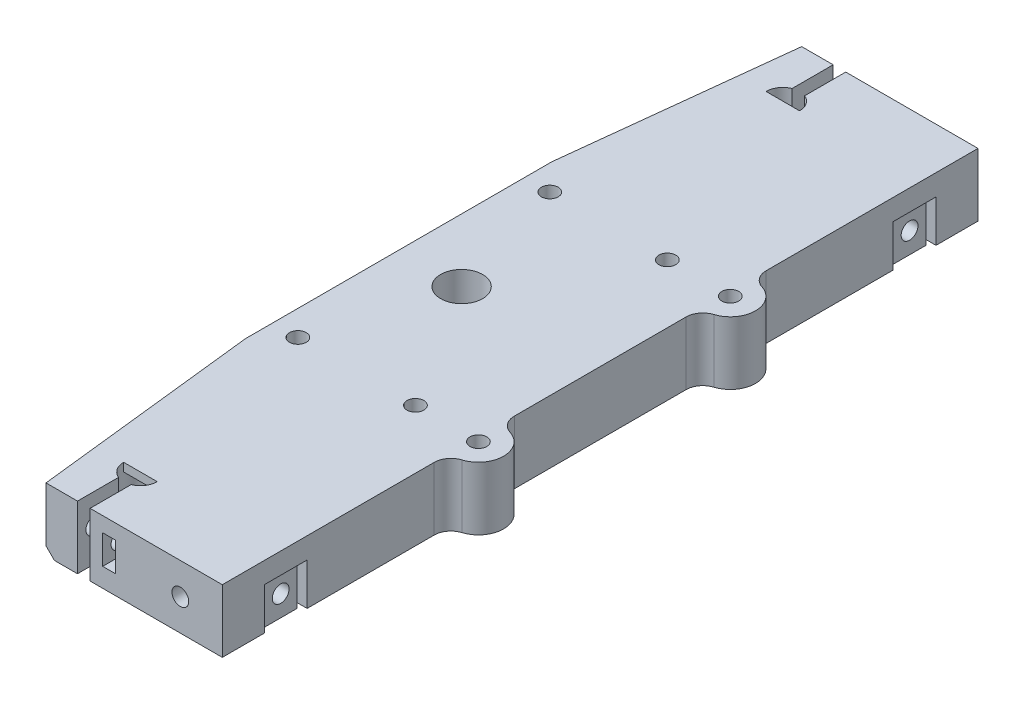
SolidWorks part; units mm, degrees
ref_plane "Płaszczyzna przednia" through (0, 0, 0) normal (0, 0, 1) x (1, 0, 0)
ref_plane "Płaszczyzna górna" through (0, 0, 0) normal (0, 1, 0) x (1, 0, 0)
ref_plane "Płaszczyzna prawa" through (0, 0, 0) normal (1, 0, 0) x (0, 0, -1)
sketch "Szkic1" plane through (0, 0, 0) normal (0, 1, 0) x (1, 0, 0)
  line L0 (-20.5, 36.5) -> (-14.5, 90)
  line L1 (27.5, -90) -> (-14.5, -90)
  line L2 (27.5, -90) -> (27.5, 90)
  line L3 (27.5, 90) -> (-14.5, 90)
  line L4 (-20.5, -36.5) -> (-20.5, 36.5)
  line L5 (27.5, 0) -> (-46.9742, 0) construction
  line L6 (-7, -80.2081) -> (-7, -90)
  line L7 (-20.5, -36.5) -> (-14.5, -90)
  line L8 (-4, -80.2081) -> (-4, -90)
  line L9 (-7, 80.2081) -> (-7, 90)
  line L10 (-4, 80.2081) -> (-4, 90)
  circle A0 centre (-14.5, 30) radius 2
  circle A1 centre (13.5, 30) radius 2
  circle A4 centre (13.5, -30) radius 2
  circle A5 centre (-14.5, -30) radius 2
  circle A6 centre (-5.5, -76.5) radius 4
  circle A7 centre (-5.5, 0) radius 5
  circle A8 centre (-5.5, 76.5) radius 4
  point P0 (0, 0)
  dimension "D7" = 6
  dimension "D10" = 4
  dimension "D11" = 30
  dimension "D12" = 15
  dimension "D13" = 10
  dimension "D16" = 8
  dimension "D1" = 48
  dimension "D2" = 180
  dimension "D3" = 27.5
  dimension "D4" = 90
  dimension "D5" = 42
  dimension "D6" = 73
  dimension "D8" = 28
  dimension "D14" = 13.5
  dimension "D15" = 15
  dimension "D17" = 3
  dimension "D19" = 13.5
  dimension "D20" = 3
extrude "Dodanie-wyciągnięcie1" add sketch "Szkic1" along normal blind 15 contours L2 L5 A7 L4 L7 L1 L6 A6 L8 A5 A4 | L5 L2 L3 L10 A8 L9 L0 L4 A7 A0 A1 region at (4.6694, 0, -43.745) region at (4.6694, 0, 43.745)
sketch "Szkic3" plane through (0, 15, 0) normal (0, 1, 0) x (1, 0, 0)
  line L0 (-9.5, 76.5) -> (-1.5, 76.5)
  line L1 (-9.5, -76.5) -> (-1.5, -76.5)
  arc A0 (-7, 80.2081) -> (-4, 80.2081) centre (-5.5, 76.5) ccw construction
  arc A1 (-4, -80.2081) -> (-7, -80.2081) centre (-5.5, -76.5) ccw construction
  arc A2 (-7, 80.2081) -> (-4, 80.2081) centre (-5.5, 76.5) ccw
  arc A3 (-4, -80.2081) -> (-7, -80.2081) centre (-5.5, -76.5) ccw
  arc M7 (-4, 80.2081) -> (-7, 80.2081) centre (-5.5, 76.5) cw
  arc M15 (-7, -80.2081) -> (-4, -80.2081) centre (-5.5, -76.5) cw
extrude "Dodanie-wyciągnięcie3" add sketch "Szkic3" against normal blind 2 contours L1 M15 | L0 M7 region at (-5.5, 15, -74.8023) region at (-5.5, 15, 74.8023)
sketch "Szkic4" plane through (0, 15, 0) normal (0, 1, 0) x (1, 0, 0)
  circle A0 centre (28.5, -30) radius 2
  circle A1 centre (28.5, 30) radius 2
  circle A2 centre (13.5, 30) radius 2 construction
  circle A3 centre (13.5, -30) radius 2 construction
  circle A4 centre (13.5, 30) radius 2
  circle A5 centre (13.5, -30) radius 2
  circle A6 centre (28.5, -30) radius 6
  circle A7 centre (28.5, 30) radius 6
  line M4 (27.5, -90) -> (27.5, 90)
  dimension "D1" = 4
  dimension "D2" = 4
  dimension "D4" = 12
  dimension "D5" = 12
  dimension "D3" = 15
extrude "Dodanie-wyciągnięcie4" add sketch "Szkic4" against normal blind 15 contours A6 A0 M4 | A7 A1 M4 region at (30.8051, 15, 30) region at (30.8051, 15, -30)
sketch "Szkic5" plane through (0, 15, 0) normal (0, 1, 0) x (1, 0, 0)
  line L16 (27.5, -90) -> (27.5, -35.9161)
  line L17 (27.5, -24.0839) -> (27.5, 24.0839)
  line L18 (27.5, 35.9161) -> (27.5, 90)
  line L19 (27.5, 90) -> (-4, 90)
  line L20 (-4, 90) -> (-4, 80.2081)
  line L21 (-1.5, 76.5) -> (-9.5, 76.5)
  line L22 (-7, 80.2081) -> (-7, 90)
  line L23 (-7, 90) -> (-14.5, 90)
  line L24 (-14.5, 90) -> (-20.5, 36.5)
  line L25 (-20.5, 36.5) -> (-20.5, -36.5)
  line L26 (-20.5, -36.5) -> (-14.5, -90)
  line L27 (-14.5, -90) -> (-7, -90)
  line L28 (-7, -90) -> (-7, -80.2081)
  line L29 (-9.5, -76.5) -> (-1.5, -76.5)
  line L30 (-4, -80.2081) -> (-4, -90)
  line L31 (-4, -90) -> (27.5, -90)
  line L32 (27.5, -90) -> (27.5, -35.9161)
  line L33 (27.5, -24.0839) -> (27.5, 24.0839)
  line L34 (27.5, 35.9161) -> (27.5, 90)
  line L35 (27.5, 90) -> (-4, 90)
  line L36 (-4, 90) -> (-4, 80.2081)
  line L37 (-1.5, 76.5) -> (-9.5, 76.5)
  line L38 (-7, 80.2081) -> (-7, 90)
  line L39 (-7, 90) -> (-14.5, 90)
  line L40 (-14.5, 90) -> (-20.5, 36.5)
  line L41 (-20.5, 36.5) -> (-20.5, -36.5)
  line L42 (-20.5, -36.5) -> (-14.5, -90)
  line L43 (-14.5, -90) -> (-7, -90)
  line L44 (-7, -90) -> (-7, -80.2081)
  line L45 (-9.5, -76.5) -> (-1.5, -76.5)
  line L46 (-4, -80.2081) -> (-4, -90)
  line L47 (-4, -90) -> (27.5, -90)
  arc A0 (27.5, 28.2679) -> (27.5, 31.7321) centre (28.5, 30) ccw construction
  arc A1 (27.5, 28.2679) -> (27.5, 31.7321) centre (28.5, 30) ccw
  arc A2 (27.5, -31.7321) -> (27.5, -28.2679) centre (28.5, -30) ccw construction
  arc A3 (27.5, -31.7321) -> (27.5, -28.2679) centre (28.5, -30) ccw
  circle A4 centre (28.5, 30) radius 2
  circle A5 centre (28.5, -30) radius 2
  arc A6 (27.5, -35.9161) -> (27.5, -24.0839) centre (28.5, -30) ccw
  arc A7 (27.5, 24.0839) -> (27.5, 35.9161) centre (28.5, 30) ccw
  arc A8 (-1.5, 76.5) -> (-4, 80.2081) centre (-5.5, 76.5) ccw
  arc A9 (-7, 80.2081) -> (-9.5, 76.5) centre (-5.5, 76.5) ccw
  arc A10 (-9.5, -76.5) -> (-7, -80.2081) centre (-5.5, -76.5) ccw
  arc A11 (-4, -80.2081) -> (-1.5, -76.5) centre (-5.5, -76.5) ccw
  arc A12 (27.5, -35.9161) -> (27.5, -24.0839) centre (28.5, -30) ccw
  arc A13 (27.5, 24.0839) -> (27.5, 35.9161) centre (28.5, 30) ccw
  arc A14 (-1.5, 76.5) -> (-4, 80.2081) centre (-5.5, 76.5) ccw
  arc A15 (-7, 80.2081) -> (-9.5, 76.5) centre (-5.5, 76.5) ccw
  arc A16 (-9.5, -76.5) -> (-7, -80.2081) centre (-5.5, -76.5) ccw
  arc A17 (-4, -80.2081) -> (-1.5, -76.5) centre (-5.5, -76.5) ccw
  arc M23 (27.5, 31.7321) -> (27.5, 28.2679) centre (28.5, 30) cw
  line M24 (27.5, 28.2679) -> (27.5, 31.7321)
  arc M25 (27.5, -28.2679) -> (27.5, -31.7321) centre (28.5, -30) cw
  line M26 (27.5, -31.7321) -> (27.5, -28.2679)
  dimension "D2" = 4
  dimension "D3" = 4
  dimension "D1" = 0
extrude "Wytnij-wyciągnięcie1" cut sketch "Szkic5" against normal blind 15 contours M25 M26 | A5 M26 | A4 M24 | M23 M24 region at (28.8427, 15, -30) region at (27.09, 15, -30) region at (28.8427, 15, 30) region at (27.09, 15, 30)
fillet "Zaokrąglenie1" radius 4 4 edges at (27.5, 7.5, -35.9161) (27.5, 7.5, -24.0839) (27.5, 7.5, 24.0839) (27.5, 7.5, 35.9161)
chamfer "Sfazowanie1" distance 2 angle 45 3 edges at (-17.5, 0, -63.25) (-17.5, 0, 63.25) (-20.5, 0, 0)
sketch "Szkic8" plane through (-4, 0, 0) normal (-1, 0, 0) x (0, 0, 1)
  line L0 (90, 15) -> (90, 0) construction
  line L1 (80.2081, 15) -> (90, 15) construction
  circle A0 centre (86, 8) radius 2
  dimension "D1" = 4
  dimension "D2" = 4
  dimension "D3" = 7
extrude "Wytnij-wyciągnięcie3" cut sketch "Szkic8" along normal through all and the other way blind 7
sketch "Szkic9" plane through (-4, 0, 0) normal (-1, 0, 0) x (0, 0, 1)
  circle A0 centre (86, 8) radius 3.5
  dimension "D1" = 7
extrude "Wytnij-wyciągnięcie4" cut sketch "Szkic9" along normal blind 4 from offset 8
sketch "Szkic10" plane through (-4, 0, 0) normal (-1, 0, 0) x (0, 0, 1)
  line L0 (86, 11.4641) -> (90, 11.4641)
  line L1 (86, 11.4641) -> (83, 9.7321)
  line L2 (83, 9.7321) -> (83, 6.2679)
  line L3 (83, 6.2679) -> (86, 4.5359)
  line L4 (86, 4.5359) -> (89, 6.2679)
  line L5 (89, 6.2679) -> (89, 9.7321)
  line L6 (89, 9.7321) -> (86, 11.4641)
  line L7 (90, 15) -> (90, 0) construction
  line L8 (90, 11.4641) -> (90, 4.5359)
  line L9 (90, 4.5359) -> (86, 4.5359)
  circle A0 centre (86, 8) radius 3 construction
  circle M1 centre (86, 8) radius 2
  line M3 (90, 0) -> (90, 15)
  dimension "D1" = 6
extrude "Wytnij-wyciągnięcie5" cut sketch "Szkic10" against normal blind 3 from offset 3 contours L5 L6 L1 L2 L3 L4 M1 | L9 L0 L6 L5 L4 M3 region at (-4, 10.5187, 87.4542) region at (-4, 11.3841, 88) offset against normal yes
mirror "Lustro2" about plane through (0, 0, 0) normal (0, 0, 1) of "Wytnij-wyciągnięcie5", "Wytnij-wyciągnięcie4", "Wytnij-wyciągnięcie3"
sketch "Szkic11" plane through (0, 0, 90) normal (0, 0, 1) x (1, 0, 0)
  line L0 (27.5, 15) -> (27.5, 0) construction
  line L1 (27.5, 15) -> (-4, 15) construction
  circle A0 centre (17.5, 7.5) radius 2
  point P4 (27.5, 7.5)
  dimension "D1" = 4
  dimension "D2" = 10
  dimension "D3" = 7.5
extrude "Wytnij-wyciągnięcie6" cut sketch "Szkic11" against normal blind 7
mirror "Lustro3" about plane through (0, 0, 0) normal (0, 0, 1) of "Wytnij-wyciągnięcie6"
sketch "Szkic12" plane through (0, 0, 0) normal (0, -1, 0) x (1, 0, 0)
  line L0 (27.5, 90) -> (-4, 90) construction
  line L1 (27.5, 80) -> (17.3, 80)
  line L2 (27.5, 80) -> (27.5, 69.8)
  line L3 (27.5, 69.8) -> (17.3, 69.8)
  line L4 (17.3, 80) -> (17.3, 69.8)
  line L5 (27.5, 80) -> (17.3, 69.8) construction
  line L6 (27.5, 69.8) -> (17.3, 80) construction
  line L7 (27.5, 90) -> (27.5, 39.5394) construction
  line L8 (27.5, -39.5394) -> (27.5, -90) construction
  line L9 (18.5, 78.8) -> (26.3, 78.8)
  line L10 (18.5, 78.8) -> (18.5, 71)
  line L11 (18.5, 71) -> (26.3, 71)
  line L12 (26.3, 78.8) -> (26.3, 71)
  line L13 (18.5, 78.8) -> (26.3, 71) construction
  line L14 (18.5, 71) -> (26.3, 78.8) construction
  line L15 (27.5, -69.8) -> (17.3, -69.8)
  line L16 (27.5, -69.8) -> (27.5, -80)
  line L17 (27.5, -80) -> (17.3, -80)
  line L18 (17.3, -69.8) -> (17.3, -80)
  line L19 (27.5, -69.8) -> (17.3, -80) construction
  line L20 (27.5, -80) -> (17.3, -69.8) construction
  line L21 (27.5, -90) -> (-4, -90) construction
  line L23 (18.5, -71) -> (26.3, -71)
  line L24 (18.5, -71) -> (18.5, -78.8)
  line L25 (18.5, -78.8) -> (26.3, -78.8)
  line L26 (26.3, -71) -> (26.3, -78.8)
  line L27 (18.5, -71) -> (26.3, -78.8) construction
  line L28 (18.5, -78.8) -> (26.3, -71) construction
  point P0 (22.4, 74.9)
  point P5 (22.4, -74.9)
  point P11 (22.4, 74.9)
  point P23 (22.4, -74.9)
  line M14 (27.5, -90) -> (27.5, -39.5394)
  line M22 (27.5, 39.5394) -> (27.5, 90)
  dimension "D1" = 10.2
  dimension "D2" = 20.2
  dimension "D3" = 7.8
  dimension "D4" = 10.2
  dimension "D5" = 20.2
  dimension "D6" = 7.8
extrude "Wytnij-wyciągnięcie7" cut sketch "Szkic12" against normal blind 10 contours L1 L4 L3 L9 L12 L11 L10 M22 | L15 L18 L17 L23 L26 L25 L24 M14 region at (27.3558, 0, 74.9) region at (27.3558, 0, -74.9)
sketch "Szkic13" plane through (26.3, 0, 0) normal (1, 0, 0) x (0, 0, -1)
  line L0 (78.8, 10) -> (78.8, 0) construction
  line L2 (80, 10) -> (69.8, 10) construction
  line L3 (-71, 10) -> (-71, 0) construction
  circle A0 centre (74.9, 5) radius 2
  circle A1 centre (-74.9, 5) radius 2
  point P6 (0, 0)
  dimension "D1" = 3.9
  dimension "D3" = 4
  dimension "D4" = 3.9
  dimension "D2" = 5
extrude "Wytnij-wyciągnięcie8" cut sketch "Szkic13" against normal blind 8
